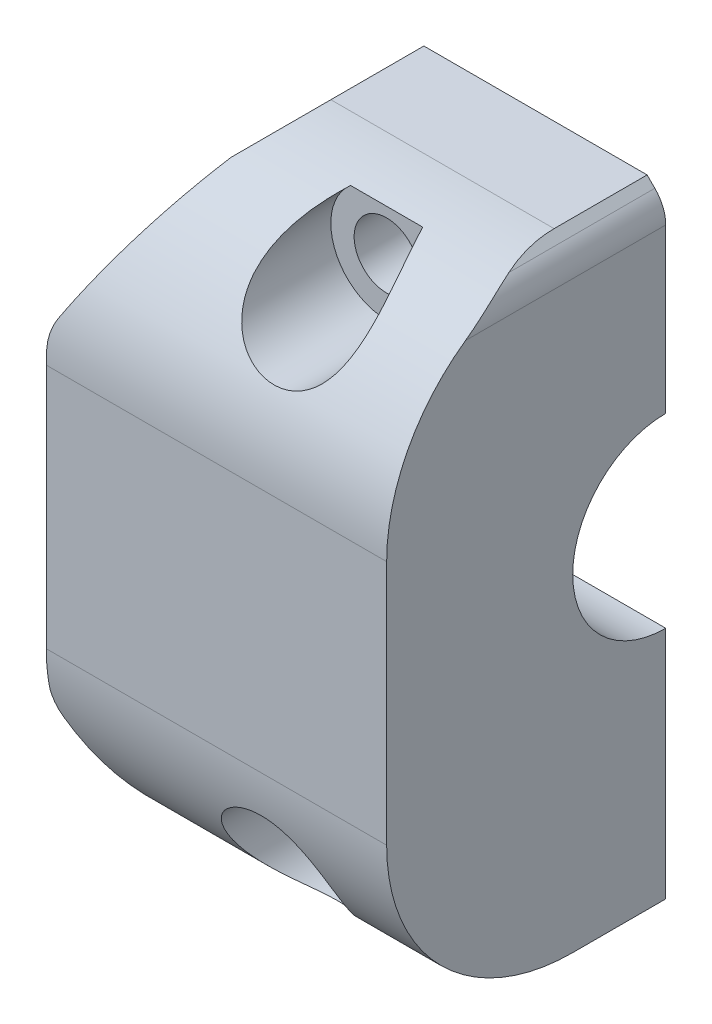
SolidWorks part; units mm, degrees
ref_plane "Front Plane" through (0, 0, 0) normal (0, 0, 1) x (1, 0, 0)
ref_plane "Top Plane" through (0, 0, 0) normal (0, 1, 0) x (1, 0, 0)
ref_plane "Right Plane" through (0, 0, 0) normal (1, 0, 0) x (0, 0, -1)
sketch "Sketch1" plane through (0, 0, 0) normal (0, 0, 1) x (1, 0, 0)
  line L0 (-110.6, 5) -> (-110.6, -5)
  line L1 (-124.6, 14.6) -> (-128.4934, 7.8564) construction
  line L2 (-124.6, 14.6) -> (-128.4934, 7.8564)
  line L3 (-110.6, -17.6) -> (-110.6, -5) construction
  line L4 (-110.6, -17.6) -> (-124.6, -17.6) construction
  line L5 (-128.4934, -10.8564) -> (-124.6, -17.6) construction
  line L6 (-128.8953, 6.3564) -> (-128.8953, -9.3564) construction
  line L7 (-110.6, -17.6) -> (-110.6, -5)
  line L8 (-110.6, -17.6) -> (-124.6, -17.6)
  line L9 (-128.4934, -10.8564) -> (-124.6, -17.6)
  line L10 (-128.8953, 6.3564) -> (-128.8953, -9.3564)
  line L16 (-124.6, -14.6) -> (-123.6, -15.6)
  line L17 (-123.6, -15.6) -> (-111.6, -15.6)
  line L18 (-111.6, -15.6) -> (-111.1858, -15.1858)
  line L19 (-110.6, -13.7716) -> (-110.6, -5)
  line L20 (-110.6, -5) -> (-115, -5)
  line L21 (-115, -5) -> (-115, -10.1)
  line L22 (-115, -10.1) -> (-120.2, -10.1)
  line L23 (-120.2, -10.1) -> (-120.2, 10.1)
  line L24 (-120.2, 10.1) -> (-115, 10.1)
  line L25 (-115, 10.1) -> (-115, 5)
  line L26 (-115, 5) -> (-110.6, 5)
  line L27 (-110.6, 5) -> (-110.6, 13.7716)
  line L28 (-111.1858, 15.1858) -> (-111.6, 15.6)
  line L29 (-111.6, 15.6) -> (-123.6, 15.6)
  line L30 (-123.6, 15.6) -> (-124.6, 14.6)
  line L31 (-124.6, 14.6) -> (-124.6, -14.6)
  line L35 (-110.6, -13.7716) -> (-110.6, -5)
  line L36 (-110.6, -5) -> (-115, -5) construction
  line L37 (-115, -5) -> (-115, -10.1) construction
  line L38 (-115, -10.1) -> (-120.2, -10.1) construction
  line L39 (-120.2, -10.1) -> (-120.2, 10.1) construction
  line L40 (-120.2, 10.1) -> (-115, 10.1) construction
  line L41 (-115, 10.1) -> (-115, 5) construction
  line L42 (-115, 5) -> (-110.6, 5) construction
  line L43 (-110.6, 5) -> (-110.6, 13.7716)
  line L44 (-111.1858, 15.1858) -> (-111.6, 15.6)
  line L45 (-111.6, 15.6) -> (-123.6, 15.6)
  line L46 (-123.6, 15.6) -> (-124.6, 14.6)
  arc A0 (-128.8953, -9.3564) -> (-128.4934, -10.8564) centre (-125.8953, -9.3564) ccw construction
  arc A1 (-128.4934, 7.8564) -> (-128.8953, 6.3564) centre (-125.8953, 6.3564) ccw construction
  arc A2 (-111.1858, -15.1858) -> (-110.6, -13.7716) centre (-112.6, -13.7716) ccw
  arc A3 (-110.6, 13.7716) -> (-111.1858, 15.1858) centre (-112.6, 13.7716) ccw
  arc A5 (-110.6, 13.7716) -> (-111.1858, 15.1858) centre (-112.6, 13.7716) ccw
  arc A6 (-128.8953, -9.3564) -> (-128.4934, -10.8564) centre (-125.8953, -9.3564) ccw
  arc A7 (-128.4934, 7.8564) -> (-128.8953, 6.3564) centre (-125.8953, 6.3564) ccw
  dimension "D1" = 0
extrude "Boss-Extrude1" add sketch "Sketch1" along normal blind 15 contours L2 A7 L10 A6 L9 L8 L7 L0 L43 A5 L44 L45 L46 region at (-116.1829, 0, 0) region at (-112.8, 5.342, 0) region at (-124.6065, -4.7343, 0)
sketch "Sketch3" plane through (-110.6, 0, 0) normal (1, 0, 0) x (0, 0, -1)
  circle A0 centre (0, 0) radius 5
  dimension "D1" = 10
extrude "Cut-Extrude1" cut sketch "Sketch3" against normal through all
sketch "Sketch4" plane through (-110.6, 0, 0) normal (1, 0, 0) x (0, 0, -1)
  circle A0 centre (0, 0) radius 10.1
  dimension "D1" = 20.2
sketch "Sketch5" plane through (0, 0, 0) normal (0, 0, -1) x (-1, 0, 0)
  line L0 (117.6, 15.6) -> (117.6, -17.6) construction
  line L3 (110.6, -17.6) -> (124.6, -17.6) construction
  line L4 (111.6, 15.6) -> (123.6, 15.6) construction
  circle A0 centre (117.6, 12.85) radius 1.75
  circle A1 centre (117.6, -12.85) radius 1.75
  dimension "D1" = 4.75
  dimension "D2" = 2.75
  dimension "D3" = 3.5
extrude "Cut-Extrude3" cut sketch "Sketch5" against normal through all
sketch "Sketch6" plane through (0, 0, 0) normal (0, 0, -1) x (-1, 0, 0)
  circle A0 centre (117.6, 12.85) radius 3
  circle A1 centre (117.6, -12.85) radius 3
  dimension "D1" = 6
extrude "Cut-Extrude4" cut sketch "Sketch6" against normal through all from offset 8 offset against normal yes
fillet "Fillet1" radius 10 2 edges at (-114.0005, 15.6, 15) (-117.6, -17.6, 15)
